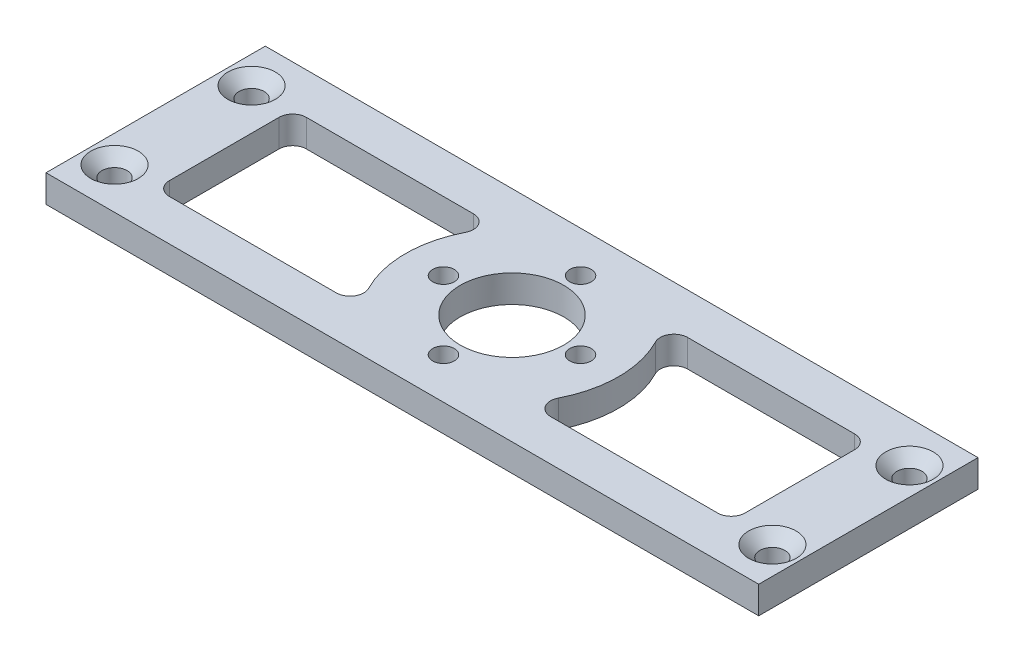
SolidWorks part; units mm, degrees
material "6061 Alloy"
ref_plane "Front" through (0, 0, 0) normal (0, 0, 1) x (1, 0, 0)
ref_plane "Top" through (0, 0, 0) normal (0, 1, 0) x (1, 0, 0)
ref_plane "Right" through (0, 0, 0) normal (1, 0, 0) x (0, 0, -1)
sketch "Sketch1" plane through (0, 0, 0) normal (0, 1, 0) x (1, 0, 0)
  line L1 (-41.275, -12.7) -> (41.275, -12.7)
  line L2 (-41.275, -12.7) -> (-41.275, 12.7)
  line L3 (-41.275, 12.7) -> (41.275, 12.7)
  line L4 (41.275, -12.7) -> (41.275, 12.7)
  line L5 (-41.275, -12.7) -> (41.275, 12.7) construction
  line L6 (-41.275, 12.7) -> (41.275, -12.7) construction
  point P0 (0, 0)
  dimension "D1" = 25.4
  dimension "D2" = 82.55
extrude "Boss-Extrude1" add sketch "Sketch1" along normal mid plane 3.175 contours L3 L4 L1 L2
sketch "Sketch2" plane through (0, 1.5875, 0) normal (0, 1, 0) x (1, 0, 0)
  point P0 (0, 0)
hole_wizard "Ø12.0mm Dowel Hole1" positions "Sketch3" profile "Sketch5" hole size "Ø12.0" standard "ANSI Metric" end condition up to next
sketch "Sketch3" plane through (0, 1.5875, 0) normal (0, 1, 0) x (1, 0, 0)
  point P0 (0, 0)
sketch "Sketch5" plane through (0, 1.5875, 0) normal (1, 0, 0) x (0, 0, 1)
  line L0 (0, 0) -> (0, 3.175)
  line L1 (0, 3.175) -> (6, 3.175)
  line L2 (6, 3.175) -> (6, 0)
  line L5 (6, 0) -> (0, 0)
  line L11 (0, -6.35) -> (0, 107.95) construction
  dimension "Thru Hole Dia." = 12
  dimension "Thru Hole Depth" = 3.175
ref_axis "Axis1" through (0, -19.8743, 0) along (0, 1, 0)
sketch "Sketch6" plane through (0, 1.5875, 0) normal (0, 1, 0) x (1, 0, 0)
  circle A0 centre (0, 0) radius 7.9375 construction
  point P3 (0, 7.9375)
  point P4 (-7.9375, 0)
  point P5 (7.9375, 0)
  point P6 (0, -7.9375)
  dimension "D1" = 15.875
hole_wizard "M3x0.5 Tapped Hole1" positions "Sketch7" profile "Sketch9" tap size "M3x0.5" standard "ANSI Metric" end condition up to next
sketch "Sketch7" plane through (0, 1.5875, 0) normal (0, 1, 0) x (1, 0, 0)
  point P0 (0, 7.9375)
  point P3 (-7.9375, 0)
  point P6 (7.9375, 0)
  point P9 (0, -7.9375)
sketch "Sketch9" plane through (0, 1.5875, -7.9375) normal (1, 0, 0) x (0, 0, 1)
  line L0 (0, 0) -> (0, 3.175)
  line L1 (0, 3.175) -> (1.25, 3.175)
  line L2 (1.25, 3.175) -> (1.25, 0)
  line L5 (1.25, 0) -> (0, 0)
  line L11 (0, -6.35) -> (0, 107.95) construction
  dimension "Thru Tap Drill Dia." = 2.5
  dimension "Thru Tap Drill Depth" = 3.175
cosmetic thread "Hole Thread5" parameters "D2"=3
cosmetic thread "Hole Thread6" parameters "D2"=3
cosmetic thread "Hole Thread7" parameters "D2"=3
cosmetic thread "Hole Thread8" parameters "D2"=3
sketch "Sketch10" plane through (0, 1.5875, 0) normal (0, 1, 0) x (1, 0, 0)
  line L0 (-41.275, -12.7) -> (-41.275, 12.7) construction
  line L1 (-38.1, 7.9375) -> (-38.1, -7.9375) construction
  line L2 (-50, 0) -> (50, 0) construction
  point P0 (-38.1, 7.9375)
  point P1 (-38.1, -7.9375)
  point P2 (-38.1, 0)
  dimension "D1" = 3.175
  dimension "D2" = 15.875
hole_wizard "CSK for M2.5 Flat Head Machine Screw1" positions "Sketch11" profile "Sketch13" countersink size "M2.5" standard "ANSI Metric" end condition up to next
sketch "Sketch11" plane through (0, 1.5875, 0) normal (0, 1, 0) x (1, 0, 0)
  point P0 (-38.1, 7.9375)
  point P3 (-38.1, -7.9375)
sketch "Sketch13" plane through (-38.1, 1.5875, -7.9375) normal (1, 0, 0) x (0, 0, 1)
  line L0 (0, 0) -> (0, 3.175)
  line L1 (0, 3.175) -> (1.45, 3.175)
  line L2 (1.45, 3.175) -> (1.45, 1.3)
  line L3 (1.45, 1.3) -> (2.75, 0)
  line L5 (2.75, 0) -> (0, 0)
  line L6 (-1.45, 1.3) -> (-2.75, 0) construction
  line L11 (0, -6.35) -> (0, 107.95) construction
  dimension "Thru Hole Dia." = 2.9
  dimension "Thru Hole Depth" = 3.175
  dimension "Near C'Sink Dia." = 5.5
  dimension "Near C'Sink Angle" = 90
mirror "Mirror1" about plane through (0, 0, 0) normal (1, 0, 0) of "CSK for M2.5 Flat Head Machine Screw1"
sketch "Sketch14" plane through (0, 1.5875, 0) normal (0, 1, 0) x (1, 0, 0)
  line L0 (-33.3375, 7.9375) -> (-33.3375, -7.9375)
  line L1 (-33.3375, -7.9375) -> (-9.4614, -7.9375)
  line L2 (-33.3375, 7.9375) -> (-9.4614, 7.9375)
  line L3 (-50, 0) -> (50, 0) construction
  line L4 (-38.1, 7.9375) -> (-38.1, -7.9375) construction
  line L5 (-41.275, 12.7) -> (41.275, 12.7) construction
  arc A0 (-9.4614, 7.9375) -> (-9.4614, -7.9375) centre (0, 0) ccw
  circle A1 centre (0, 0) radius 6 construction
  point P2 (-33.3375, 0)
  point P10 (0, 0)
  dimension "D3" = 6.35
  dimension "D1" = 4.7625
  dimension "D2" = 4.7625
extrude "Cut-Extrude1" cut sketch "Sketch14" against normal through all
mirror "Mirror2" about plane through (0, 0, 0) normal (1, 0, 0) of "Cut-Extrude1"
fillet "Fillet1" radius 1.5875 8 edges at (9.4614, 0, -7.9375) (9.4614, 0, 7.9375) (33.3375, 0, 7.9375) (33.3375, 0, -7.9375) (-9.4614, 0, -7.9375) (-9.4614, 0, 7.9375) (-33.3375, 0, 7.9375) (-33.3375, 0, -7.9375)
